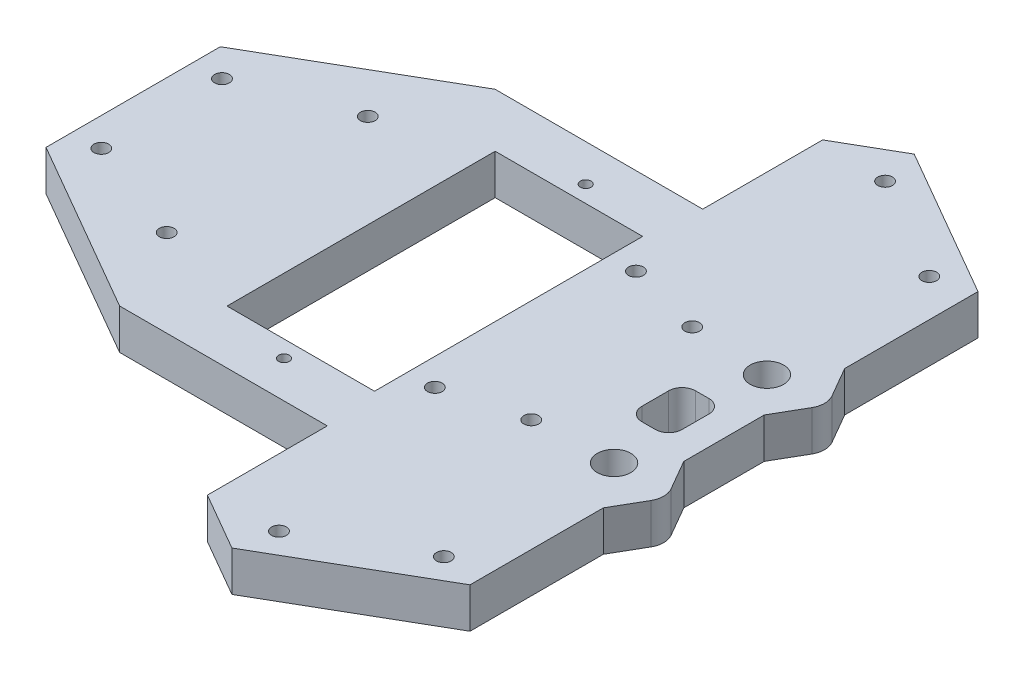
SolidWorks part; units mm, degrees
material "Acrylic (Medium-high impact)"
ref_plane "Front Plane" through (0, 0, 0) normal (0, 0, 1) x (1, 0, 0)
ref_plane "Top Plane" through (0, 0, 0) normal (0, 1, 0) x (1, 0, 0)
ref_plane "Right Plane" through (0, 0, 0) normal (1, 0, 0) x (0, 0, -1)
sketch "Sketch1" plane through (0, 0, 0) normal (0, 1, 0) x (1, 0, 0)
  line L0 (4.75, -20) -> (-17.25, -20)
  line L1 (-17.25, -20) -> (-17.25, 20)
  line L2 (-17.25, 20) -> (4.75, 20)
  line L3 (25.625, 44.3838) -> (23.5, 40.7032) construction
  line L4 (0, 0) -> (23.5, -40.7032) construction
  line L5 (0, 0) -> (-47, 0) construction
  line L6 (4.75, 20) -> (4.75, -20)
  line L7 (14.3667, 50.8838) -> (36.8833, 37.8838)
  line L8 (31.8833, 12) -> (31.8833, -12) construction
  line L9 (15.7058, 45.2032) -> (31.2942, 36.2032) construction
  line L10 (31.2942, -36.2032) -> (15.7058, -45.2032) construction
  line L11 (-47, 9) -> (-47, -9) construction
  line L12 (23.5, 40.7032) -> (0, 0) construction
  line L13 (23.5, -40.7032) -> (25.625, -44.3838) construction
  line L14 (-47, 0) -> (-51.25, 0) construction
  line L15 (0, 0) -> (31.8833, 0) construction
  line L16 (36.8833, 37.8838) -> (36.8833, -37.8838)
  line L17 (36.8833, -37.8838) -> (14.3667, -50.8838)
  line L22 (-51.25, 13) -> (-51.25, -13)
  line L23 (14.3667, 50.8838) -> (5.7064, 45.8838)
  line L24 (14.3667, -50.8838) -> (5.7064, -45.8838)
  line L25 (5.7064, 45.8838) -> (5.7064, 28)
  line L26 (5.7064, 28) -> (-25.2692, 28)
  line L27 (-25.2692, 28) -> (-51.25, 13)
  line L28 (5.7064, -45.8838) -> (5.7064, -28)
  line L29 (5.7064, -28) -> (-25.2692, -28)
  line L30 (-25.2692, -28) -> (-51.25, -13)
  line L69 (25.7064, -23.5) -> (25.7064, 0) construction
  line L70 (25.7064, 0) -> (25.7064, 23.5) construction
  line L71 (26.6333, -4) -> (32.6333, -4)
  line L72 (26.6333, -4) -> (26.6333, 4)
  line L73 (26.6333, 4) -> (32.6333, 4)
  line L74 (32.6333, -4) -> (32.6333, 4)
  line L75 (26.6333, -4) -> (32.6333, 4) construction
  line L76 (26.6333, 4) -> (32.6333, -4) construction
  circle A0 centre (15.7058, 45.2032) radius 1.1
  circle A1 centre (31.2942, 36.2032) radius 1.1
  circle A2 centre (31.2942, -36.2032) radius 1.1
  circle A3 centre (15.7058, -45.2032) radius 1.1
  circle A4 centre (-47, 9) radius 1.1
  circle A5 centre (-47, -9) radius 1.1
  circle A7 centre (15.7058, 45.2032) radius 2.5 construction
  point P4 (-18.25, 0)
  point P85 (0, 0)
  point P92 (4.75, 0)
  point P93 (0, 0)
  point P114 (29.6333, 0)
  point P148 (0, 0)
  dimension "D2" = 2.2
  dimension "D7" = 5
  dimension "D9" = 26
  dimension "D11" = 47
  dimension "D12" = 5
  dimension "D13" = 34
  dimension "D10" = 56
  dimension "D1" = 18
  dimension "D3" = 4.25
  dimension "D4" = 120
  dimension "D5" = 40
  dimension "D6" = 22
  dimension "D15" = 10
  dimension "D22" = 51.25
  dimension "D33" = 8
  dimension "D34" = 6
  dimension "D35" = 7.25
extrude "Boss-Extrude1" add sketch "Sketch1" along normal blind 6
sketch "Sketch10" plane through (0, 0, 0) normal (0, -1, 0) x (1, 0, 0)
  line L0 (-6.25, 22.5) -> (-6.25, -22.5) construction
  line L1 (4.75, 20) -> (4.75, -20) construction
  line L2 (4.75, -20) -> (-17.25, -20) construction
  point P4 (4.75, 0)
  point P5 (-6.25, 0)
  point P8 (-6.25, -20)
  dimension "D1" = 45
hole_wizard "Ø1.6 (1.6) Diameter Hole3" positions "3DSketch1" profile "Sketch11" hole size "Ø1.6" standard "ISO" end condition through all
sketch3d "3DSketch1"
  point P0 (-6.25, 0, 22.5)
  point P3 (-6.25, 0, -22.5)
sketch "Sketch11" plane through (-6.25, 0, 22.5) normal (1, 0, 0) x (0, 0, -1)
  line L0 (0, 0) -> (0, 6)
  line L1 (0, 6) -> (0.8, 6)
  line L2 (0.8, 6) -> (0.8, 0)
  line L5 (0.8, 0) -> (0, 0)
  line L11 (0, -6.35) -> (0, 107.95) construction
  dimension "Thru Hole Dia." = 1.6
  dimension "Thru Hole Depth" = 6
sketch "Sketch9" plane through (0, 0, 0) normal (0, -1, 0) x (1, 0, 0)
  line L0 (33.0083, -12) -> (30.7583, -12) construction
  line L1 (36.8833, 37.8838) -> (36.8833, -37.8838) construction
  line L2 (39.4814, 13.5) -> (36.8833, 18)
  line L3 (39.4814, 10.5) -> (36.8833, 6)
  line L4 (33.0083, 12) -> (30.7583, 12) construction
  line L5 (36.8833, 0) -> (0, 0) construction
  line L6 (36.8833, -18) -> (36.8833, -6)
  line L7 (39.4814, -10.5) -> (36.8833, -6)
  line L8 (39.4814, -13.5) -> (36.8833, -18)
  line L12 (36.8833, 18) -> (36.8833, 6)
  arc A0 (36.8833, 9) -> (36.8833, 15) centre (36.8833, 12) ccw
  arc A3 (36.8833, -9) -> (36.8833, -15) centre (36.8833, -12) cw
  dimension "D1" = 6
  dimension "D2" = 6
  dimension "D3" = 6
extrude "Boss-Extrude2" add sketch "Sketch9" against normal up to surface (6 mm away) contours A3 L6 | L6 A3 L7 | L8 A3 L6 | L12 A0 | A0 L12 L3 | A0 L2 L12 region at (37.6134, 0, 15.7936) region at (38.1566, 0, 12) region at (37.6134, 0, 8.2064) region at (37.6134, 0, -15.7936) region at (38.1566, 0, -12) region at (37.6134, 0, -8.2064) up to face at (-6.25, 6, 21.7)
fillet "Fillet1" radius 2 4 edges at (26.6333, 3, -4) (26.6333, 3, 4) (32.6333, 3, 4) (32.6333, 3, -4)
sketch "Sketch13" plane through (0, 6, 0) normal (0, 1, 0) x (1, 0, 0)
  line L0 (20.1333, 12) -> (20.1333, -12) construction
  line L1 (20.1333, 0) -> (34.6333, 0) construction
  line L2 (26.6333, 2) -> (26.6333, -2) construction
  line L3 (36.8833, -6) -> (36.8833, 6) construction
  line L4 (39.8833, 11.4) -> (31.8833, 11.4) construction
  line L5 (39.8833, -11.4) -> (31.8833, -11.4) construction
  point P7 (26.6333, 0)
  point P11 (0, 0)
  point P12 (0, 0)
  dimension "D1" = 24
  dimension "D2" = 2.25
  dimension "D3" = 14.5
  dimension "D4" = 8
  dimension "D5" = 0.6
  dimension "D6" = 11.75
hole_wizard "Ø2.2 (2.2) Diameter Hole1" positions "3DSketch2" profile "Sketch14" hole size "Ø2.2" standard "ISO" end condition through all
sketch3d "3DSketch2"
  point P0 (20.1333, 6, -12)
  point P6 (20.1333, 6, 12)
sketch "Sketch14" plane through (20.1333, 6, -12) normal (1, 0, 0) x (0, 0, 1)
  line L0 (0, 0) -> (0, 6)
  line L1 (0, 6) -> (1.1, 6)
  line L2 (1.1, 6) -> (1.1, 0)
  line L5 (1.1, 0) -> (0, 0)
  line L11 (0, -6.35) -> (0, 107.95) construction
  dimension "Thru Hole Dia." = 2.2
  dimension "Thru Hole Depth" = 6
hole_wizard "Ø4.0mm Dowel Hole1" positions "3DSketch3" profile "Sketch15" hole size "Ø4.0" standard "ANSI Metric" end condition through all
sketch3d "3DSketch3"
  point P0 (31.8833, 6, -11.4)
  point P3 (31.8833, 6, 11.4)
sketch "Sketch15" plane through (31.8833, 6, -11.4) normal (1, 0, 0) x (0, 0, 1)
  line L0 (0, 0) -> (0, 6)
  line L1 (0, 6) -> (2.5, 6)
  line L2 (2.5, 6) -> (2.5, 0)
  line L5 (2.5, 0) -> (0, 0)
  line L11 (0, -6.35) -> (0, 107.95) construction
  dimension "Thru Hole Dia." = 5
  dimension "Thru Hole Depth" = 6
sketch "Dimensions" plane through (0, 6, 0) normal (0, 1, 0) x (1, 0, 0)
  line L0 (8.344, 0) -> (-110.844, 0)
  line L1 (20.1333, 0) -> (34.6333, 0) construction
  line L2 (53.736, 93.0735) -> (-2.486, -4.3059)
  line L4 (-1.5108, 2.6167) -> (52.7608, -91.3843)
  line L8 (36.8833, 6) -> (36.8833, -6)
  line L10 (14.3667, 50.8838) -> (36.8833, 37.8838)
  line L11 (-51.25, 13) -> (-51.25, -13)
  line L12 (14.3667, -50.8838) -> (36.8833, -37.8838)
  point P3 (-51.25, 0)
  point P7 (25.625, 44.3838)
  point P10 (25.625, -44.3838)
  dimension "D1" = 51.25
  dimension "D2" = 25.625
  dimension "D3" = 36.8833
  dimension "D4" = 51.25
  dimension "D5" = 51.25
  dimension "D6" = 51.25
  dimension "D7" = 88.7676
  dimension "D8" = 60
ref_point "Point1"
ref_axis "Axis1" through (0, 6, 0) along (0, 1, 0)
sketch "Sketch16" plane through (0, 6, 0) normal (0, 1, 0) x (1, 0, 0)
  line L1 (-31.25, -15) -> (8.75, -15)
  line L2 (-31.25, -15) -> (-31.25, 15)
  line L3 (-31.25, 15) -> (8.75, 15)
  line L4 (8.75, -15) -> (8.75, 15)
  line L5 (-31.25, 0) -> (8.75, 0) construction
  line L6 (8.344, 0) -> (-110.844, 0) construction
  line L7 (-17.25, 20) -> (-17.25, -20) construction
  dimension "D1" = 40
  dimension "D2" = 30
  dimension "D3" = 14
hole_wizard "Ø2.0mm Dowel Hole1" positions "3DSketch4" profile "Sketch18" hole size "Ø2.0" standard "ANSI Metric" end condition through all
sketch3d "3DSketch4"
  point P0 (-31.25, 6, -15)
  point P3 (-31.25, 6, 15)
  point P6 (8.75, 6, 15)
  point P9 (8.75, 6, -15)
sketch "Sketch18" plane through (-31.25, 6, -15) normal (1, 0, 0) x (0, 0, 1)
  line L0 (0, 0) -> (0, 6)
  line L1 (0, 6) -> (1.1, 6)
  line L2 (1.1, 6) -> (1.1, 0)
  line L5 (1.1, 0) -> (0, 0)
  line L11 (0, -6.35) -> (0, 107.95) construction
  dimension "Thru Hole Dia." = 2.2
  dimension "Thru Hole Depth" = 6
